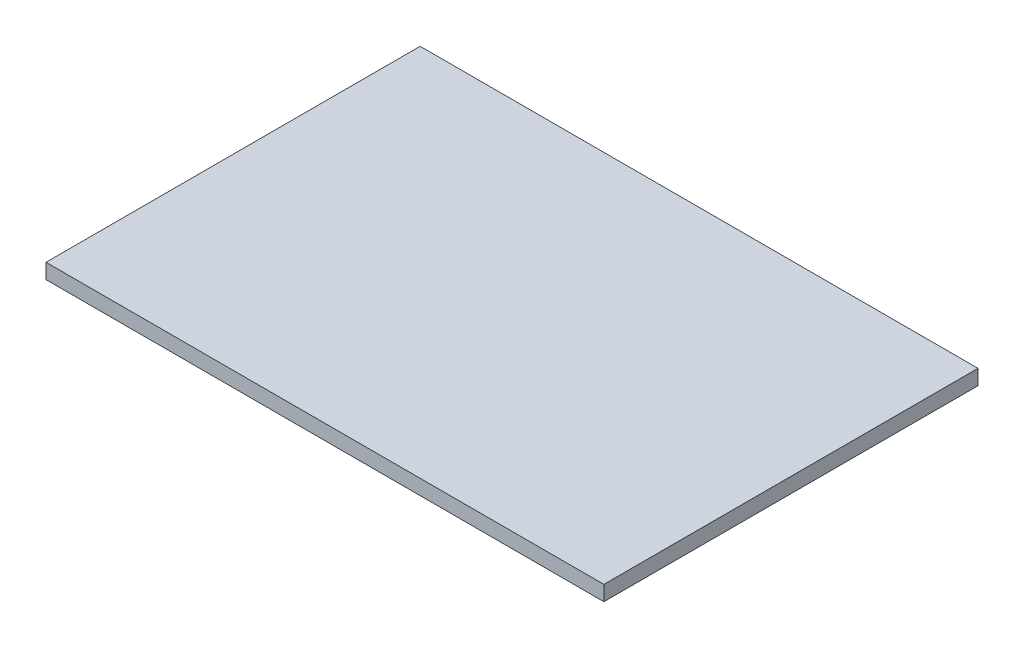
SolidWorks part; units mm, degrees
material "Perspex (TM) GS Acrylic Cast Sheet"
ref_plane "Front Plane" through (0, 0, 0) normal (0, 0, 1) x (1, 0, 0)
ref_plane "Top Plane" through (0, 0, 0) normal (0, 1, 0) x (1, 0, 0)
ref_plane "Right Plane" through (0, 0, 0) normal (1, 0, 0) x (0, 0, -1)
sketch "Sketch1" plane through (0, 0, 0) normal (0, 1, 0) x (1, 0, 0)
  line L1 (-167, -112) -> (167, -112)
  line L2 (-167, -112) -> (-167, 112)
  line L3 (-167, 112) -> (167, 112)
  line L4 (167, -112) -> (167, 112)
  line L5 (-167, -112) -> (167, 112) construction
  line L6 (-167, 112) -> (167, -112) construction
  point P0 (0, 0)
  dimension "D2" = 224
  dimension "D1" = 334
extrude "Boss-Extrude1" add sketch "Sketch1" along normal blind 9
equation "\"PCLength\"= 316mm'Length across I/O from PS to GPU"
equation "\"PCWidth\"= 242mm'Distance of longest part parallel to GPU(ussually GPU)"
equation "\"PCHeight\"= 178mm'Tallest point with mobo laying flat"
equation "\"WallThickness\"= 9mm'Thickness of each outer tank wall"
equation "\"ThermoBarrierThickness\"= 3mm'Thickness of barrier between hot side and cold side"
equation "\"HotSideGap\"= 25mm'Space in the hot side for a pump"
equation "\"PCClearance\"= 30mm'Clearance from top of tank to top of PC"
equation "\"RadiatorHeight\"= 275mm'Final Height from ground of radiators"
equation "\"D2@Sketch1\"=\"PCHeight\" + \"ThermoBarrierThickness\" + \"HotSideGap\" + (2 * \"WallThickness\")"
equation "\"D1@Boss-Extrude1\"=\"WallThickness\""
equation "\"D1@Sketch1\"=\"PCLength\" + (2 * \"WallThickness\")"
